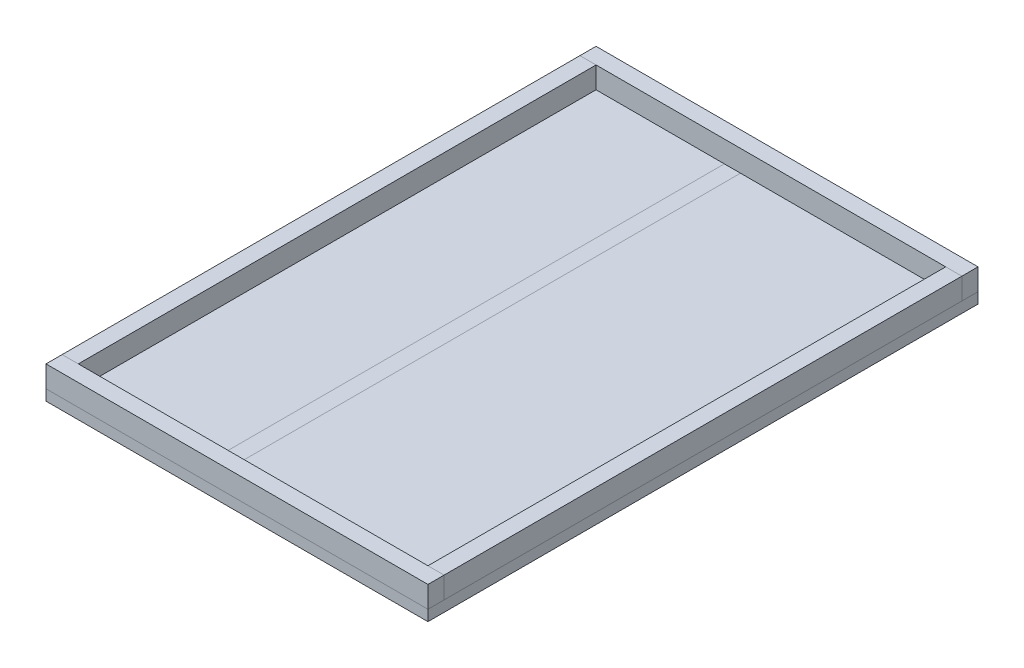
SolidWorks part; units mm, degrees
material "Oak"
ref_plane "Front Plane" through (0, 0, 0) normal (0, 0, 1) x (1, 0, 0)
ref_plane "Top Plane" through (0, 0, 0) normal (0, 1, 0) x (1, 0, 0)
ref_plane "Right Plane" through (0, 0, 0) normal (1, 0, 0) x (0, 0, -1)
sketch "Sketch1" plane through (0, 0, 0) normal (0, 1, 0) x (1, 0, 0)
  line L0 (206.35, 305.55) -> (225.4, 305.55)
  line L1 (-225.4, -324.6) -> (225.4, -324.6)
  line L2 (-225.4, -324.6) -> (-225.4, 324.6)
  line L3 (-225.4, 324.6) -> (225.4, 324.6)
  line L4 (225.4, -324.6) -> (225.4, 324.6)
  line L5 (-225.4, -324.6) -> (225.4, 324.6) construction
  line L6 (-225.4, 324.6) -> (225.4, -324.6) construction
  line L7 (-206.35, -305.55) -> (206.35, -305.55)
  line L8 (-206.35, -305.55) -> (-206.35, 305.55)
  line L9 (-206.35, 305.55) -> (206.35, 305.55)
  line L10 (206.35, -305.55) -> (206.35, 305.55)
  line L11 (-206.35, -305.55) -> (206.35, 305.55) construction
  line L12 (-206.35, 305.55) -> (206.35, -305.55) construction
  line L13 (-206.35, 305.55) -> (-225.4, 305.55)
  line L14 (-206.35, -305.55) -> (-225.4, -305.55)
  line L15 (206.35, -305.55) -> (225.4, -305.55)
  point P0 (0, 0)
  point P6 (0, 0)
  dimension "D1" = 450.8
  dimension "D2" = 649.2
  dimension "D3" = 19.05
  dimension "D4" = 19.05
extrude "Boss-Extrude1" add sketch "Sketch1" against normal blind 12.7 contours L14 L8 L13 L2 | L13 L9 L0 L4 L3 L2 | L7 L10 L9 L8 | L10 L15 L4 L0 | L15 L7 L14 L2 L1 L4 | L3 L4 L1 L2 region at (0, 0, -315.075) region at (0, 0, 0) region at (215.875, 0, 0) region at (-215.875, 0, 0) region at (0, 0, 315.075)
extrude "Boss-Extrude2" add sketch "Sketch1<3>" along normal blind 25.4 separate body contours L14 L8 L13 L2 | L10 L15 L4 L0 region at (215.875, 0, 0) region at (-215.875, 0, 0)
sketch "Sketch1<3>" plane through (0, 0, 0) normal (0, 1, 0) x (1, 0, 0) same geometry as "Sketch1"
extrude "Boss-Extrude3" add sketch "Sketch1<4>" along normal blind 25.4 separate body contours L13 L9 L0 L4 L3 L2 | L15 L7 L14 L2 L1 L4 region at (0, 0, -315.075) region at (0, 0, 315.075)
sketch "Sketch1<4>" plane through (0, 0, 0) normal (0, 1, 0) x (1, 0, 0) same geometry as "Sketch1"
sketch "Sketch4" plane through (0, -12.7, 0) normal (0, -1, 0) x (1, 0, 0)
  line L0 (225.4, -305.55) -> (-225.4, -305.55) construction
  line L1 (-225.4, 305.55) -> (225.4, 305.55) construction
  line L2 (225.4, -305.55) -> (-225.4, -305.55) construction
  line L3 (-225.4, 305.55) -> (225.4, 305.55) construction
  line L5 (-96.2, -305.55) -> (5.4, -305.55)
  line L6 (-96.2, -305.55) -> (-96.2, 305.55)
  line L7 (-96.2, 305.55) -> (5.4, 305.55)
  line L8 (5.4, -305.55) -> (5.4, 305.55)
  line L9 (-96.2, -305.55) -> (5.4, 305.55) construction
  line L10 (-96.2, 305.55) -> (5.4, -305.55) construction
  line L12 (-225.4, 324.6) -> (-225.4, -324.6) construction
  point P4 (-45.4, 0)
  dimension "D1" = 101.6
  dimension "D2" = 180
extrude "Boss-Extrude5" add sketch "Sketch4" along normal blind 12.7 separate body
sketch "Sketch2" plane through (0, 0, 0) normal (0, 1, 0) x (1, 0, 0)
  line L0 (-225.4, -305.55) -> (225.4, -305.55) construction
  line L1 (225.4, 305.55) -> (-225.4, 305.55) construction
  line L2 (-225.4, -305.55) -> (225.4, -305.55) construction
  line L3 (225.4, 305.55) -> (-225.4, 305.55) construction
  line L5 (-54.925, -305.55) -> (-35.875, -305.55)
  line L6 (-54.925, -305.55) -> (-54.925, 305.55)
  line L7 (-54.925, 305.55) -> (-35.875, 305.55)
  line L8 (-35.875, -305.55) -> (-35.875, 305.55)
  line L9 (-54.925, -305.55) -> (-35.875, 305.55) construction
  line L10 (-54.925, 305.55) -> (-35.875, -305.55) construction
  line L11 (5.4, 305.55) -> (5.4, -305.55) construction
  line L12 (-96.2, -305.55) -> (-96.2, 305.55) construction
  line L13 (5.4, 305.55) -> (5.4, -305.55) construction
  line L14 (-96.2, -305.55) -> (-96.2, 305.55) construction
  line L15 (-96.2, 0) -> (-45.4, 0) construction
  line L16 (-45.4, 0) -> (5.4, 0) construction
  point P4 (-45.4, 0)
  dimension "D1" = 19.05
extrude "Cut-Extrude1" cut sketch "Sketch2" against normal blind 12.7
extrude "Boss-Extrude4" add sketch "Sketch2<2>" against normal blind 9.525 separate body
sketch "Sketch2<2>" plane through (0, 0, 0) normal (0, 1, 0) x (1, 0, 0) same geometry as "Sketch2"
